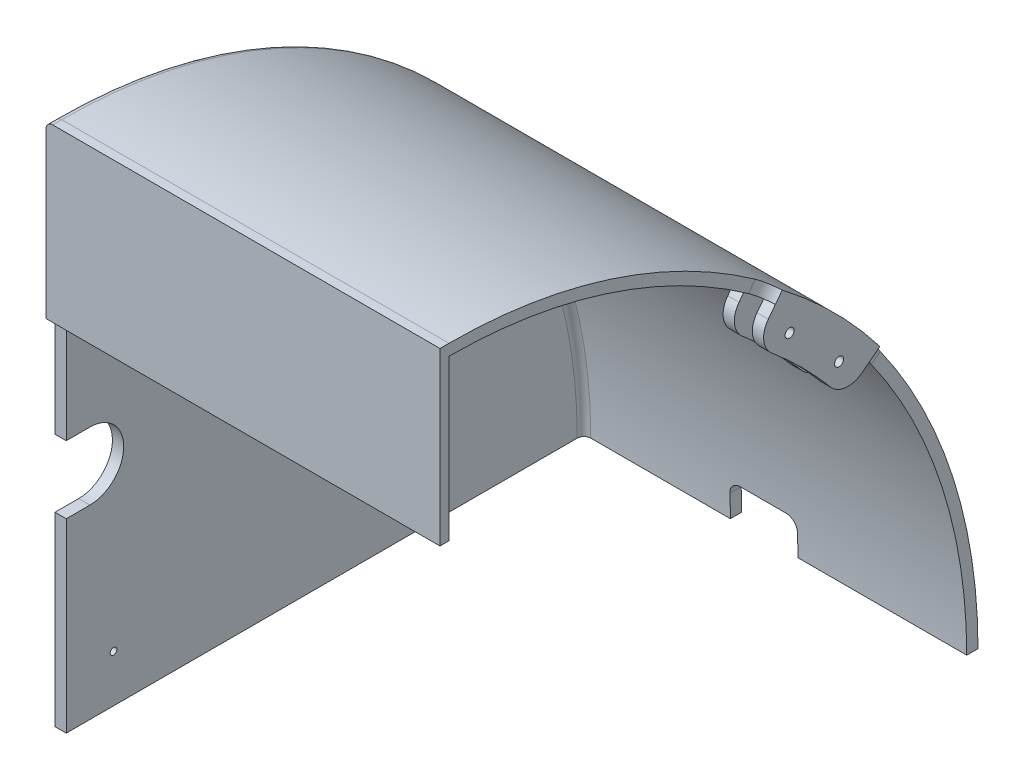
SolidWorks part; units mm, degrees
ref_plane "前视基准面" through (0, 0, 0) normal (0, 0, 1) x (1, 0, 0)
ref_plane "上视基准面" through (0, 0, 0) normal (0, 1, 0) x (1, 0, 0)
ref_plane "右视基准面" through (0, 0, 0) normal (1, 0, 0) x (0, 0, -1)
sketch "草图1" plane through (0, 0, 0) normal (1, 0, 0) x (0, 0, -1)
  circle A0 centre (0, 0) radius 235
  dimension "D1" = 470
extrude "凸台-拉伸1" add sketch "草图1" along normal blind 5
sketch "草图2" plane through (5, 0, 0) normal (1, 0, 0) x (0, 0, -1)
  circle A0 centre (0, 0) radius 230
  circle A1 centre (0, 0) radius 235
  circle A2 centre (0, 0) radius 235
  dimension "D1" = 0
  dimension "D2" = 5
extrude "凸台-拉伸2" add sketch "草图2" along normal blind 170
sketch "草图3" plane through (0, 0, 0) normal (-1, 0, 0) x (0, 0, 1)
  line L0 (0, 0) -> (0, 250)
  line L1 (0, 250) -> (330.8874, 250)
  line L2 (330.8874, 250) -> (330.8874, -253.4327)
  line L3 (330.8874, -253.4327) -> (-250, -253.4327)
  line L4 (-250, -253.4327) -> (-250, 0)
  line L5 (-250, 0) -> (0, 0)
  dimension "D1" = 250
  dimension "D2" = 250
extrude "切除-拉伸1" cut sketch "草图3" against normal through all
ref_plane "基准面1" through (167, 0, 0) normal (1, 0, 0) x (0, 0, -1)
sketch "草图4" plane through (167, 0, 0) normal (1, 0, 0) x (0, 0, -1)
  line L0 (0, 0) -> (35355.3391, 35355.3391) construction
  line L1 (230, 0) -> (0, 0) construction
  line L2 (170.571, 130.8837) -> (182.4713, 140.0151)
  line L3 (130.8837, 170.571) -> (140.0151, 182.4713)
  arc A0 (230, 0) -> (0, 230) centre (0, 0) ccw construction
  arc A1 (182.4713, 140.0151) -> (140.0151, 182.4713) centre (0, 0) ccw
  arc A2 (170.571, 130.8837) -> (130.8837, 170.571) centre (0, 0) ccw
  arc A4 (230, 0) -> (0, 230) centre (0, 0) ccw construction
  arc A5 (215, 0) -> (0, 215) centre (0, 0) ccw construction
  dimension "D2" = 45
  dimension "D3" = 7.5
  dimension "D1" = 15
extrude "凸台-拉伸3" add sketch "草图4" against normal blind 5
ref_plane "基准面2" through (59, 0, 0) normal (1, 0, 0) x (0, 0, -1)
sketch "草图5" plane through (59, 0, 0) normal (1, 0, 0) x (0, 0, -1)
  line L2 (170.571, 130.8837) -> (182.4713, 140.0151)
  line L3 (140.0151, 182.4713) -> (130.8837, 170.571)
  line L4 (170.571, 130.8837) -> (182.4713, 140.0151)
  line L5 (140.0151, 182.4713) -> (130.8837, 170.571)
  arc A2 (170.571, 130.8837) -> (130.8837, 170.571) centre (0, 0) ccw
  arc A3 (182.4713, 140.0151) -> (140.0151, 182.4713) centre (0, 0) ccw
  arc A4 (170.571, 130.8837) -> (130.8837, 170.571) centre (0, 0) ccw
  arc A5 (182.4713, 140.0151) -> (140.0151, 182.4713) centre (0, 0) ccw
  dimension "D1" = 0
extrude "凸台-拉伸4" add sketch "草图5" against normal blind 5
sketch "草图6" plane through (167, 0, 0) normal (1, 0, 0) x (0, 0, -1)
  line L2 (0, 0) -> (35355.3391, 35355.3391) construction
  line L3 (230, 0) -> (0, 0) construction
  line L4 (146.3012, 168.3002) -> (0, 0) construction
  line L5 (0, 0) -> (168.3002, 146.3012) construction
  circle A0 centre (146.3012, 168.3002) radius 2
  circle A1 centre (168.3002, 146.3012) radius 2
  dimension "D1" = 4
  dimension "D2" = 223
  dimension "D3" = 223
  dimension "D4" = 45
  dimension "D5" = 4
  dimension "D6" = 4
extrude "切除-拉伸2" cut sketch "草图6" against normal blind 5
fillet "圆角1" radius 3 2 edges at (0, 166.1701, -166.1701) (5, 162.6346, -162.6346)
sketch "草图7" plane through (175, 0, 0) normal (1, 0, 0) x (0, 0, -1)
  line L2 (170.571, 130.8837) -> (182.4713, 140.0151)
  line L3 (140.0151, 182.4713) -> (130.8837, 170.571)
  line L4 (170.571, 130.8837) -> (186.438, 143.0589)
  line L5 (143.0589, 186.438) -> (130.8837, 170.571)
  arc A0 (235, 0) -> (0, 235) centre (0, 0) ccw construction
  arc A1 (186.438, 143.0589) -> (143.0589, 186.438) centre (0, 0) ccw
  arc A2 (170.571, 130.8837) -> (130.8837, 170.571) centre (0, 0) ccw
  arc A3 (182.4713, 140.0151) -> (140.0151, 182.4713) centre (0, 0) ccw
  arc A4 (170.571, 130.8837) -> (130.8837, 170.571) centre (0, 0) ccw
  dimension "D1" = 0
extrude "凸台-拉伸5" add sketch "草图7" along normal blind 5
fillet "圆角2" radius 10 2 edges at (175, 184.4547, -141.537) (175, 141.537, -184.4547)
fillet "圆角3" radius 10 4 edges at (177.5, 130.8837, -170.571) (164.5, 130.8837, -170.571) (177.5, 170.571, -130.8837) (164.5, 170.571, -130.8837)
sketch "草图8" plane through (180, 0, 0) normal (1, 0, 0) x (0, 0, -1)
  circle A0 centre (168.3002, 146.3012) radius 2 construction
  circle A1 centre (146.3012, 168.3002) radius 2 construction
  circle A2 centre (168.3002, 146.3012) radius 2
  circle A3 centre (146.3012, 168.3002) radius 2
extrude "切除-拉伸3" cut sketch "草图8" against normal blind 5
fillet "圆角4" radius 10 2 edges at (56.5, 170.571, -130.8837) (56.5, 130.8837, -170.571)
sketch "草图11" plane through (0, 0, 0) normal (0, 0, 1) x (1, 0, 0)
  line L0 (3, 235) -> (175, 235) construction
  line L1 (3, 235) -> (175, 235)
  line L2 (0, 232) -> (0, 80) construction
  line L3 (0, 232) -> (0, 159)
  line L4 (175, 235) -> (175, 230) construction
  line L7 (0, 159) -> (175, 159)
  line L8 (175, 235) -> (175, 159)
  arc A0 (3, 235) -> (0, 232) centre (3, 232) ccw construction
  arc A1 (3, 235) -> (0, 232) centre (3, 232) ccw
  dimension "D1" = 76
extrude "凸台-拉伸7" add sketch "草图11" along normal blind 4
sketch "草图12" plane through (0, 0, 0) normal (-1, 0, 0) x (0, 0, 1)
  line L0 (0, 0) -> (-232, 0) construction
  line L2 (-101, 0) -> (-98, 0)
  line L3 (-224, 0) -> (-221, 0)
  line L6 (-161, 0) -> (-161, 50000) construction
  line L9 (-224, 0) -> (-221, 0)
  line L10 (-101, 0) -> (-98, 0)
  line L11 (-194.7226, 53.2145) -> (-193, 50.7543)
  line L12 (-203.8509, 46.1823) -> (-201.728, 44.0594)
  line L13 (-127.2774, 53.2145) -> (-129, 50.7543)
  line L14 (-118.1491, 46.1823) -> (-120.272, 44.0594)
  arc A0 (-101, 0) -> (-120.272, 44.0594) centre (-161, 0) ccw
  arc A1 (-98, 0) -> (-118.1491, 46.1823) centre (-161, 0) ccw
  circle A2 centre (-161, 0) radius 60 construction
  circle A3 centre (-161, 0) radius 63 construction
  arc A4 (-127.2774, 53.2145) -> (-194.7226, 53.2145) centre (-161, 0) ccw
  arc A5 (-129, 50.7543) -> (-193, 50.7543) centre (-161, 0) ccw
  arc A6 (-203.8509, 46.1823) -> (-224, 0) centre (-161, 0) ccw
  arc A7 (-201.728, 44.0594) -> (-221, 0) centre (-161, 0) ccw
  line M14 (-232, 0) -> (0, 0)
  dimension "D1" = 120
  dimension "D2" = 161
  dimension "D4" = 10
  dimension "D5" = 32
  dimension "D6" = 11
  dimension "D7" = 32
  dimension "D8" = 35
  dimension "D9" = 10
  dimension "D3" = 3
extrude "凸台-拉伸8" add sketch "草图12" along normal blind 20 contours A5 L13 A4 L11 | A1 L14 A0 M14 | A7 L12 A6 M14 region at (0, 24.2504, -105.559) region at (0, 0.5127, -222.5) region at (0, 62.3145, -161)
sketch "草图13" plane through (0, 0, 4) normal (0, 0, 1) x (1, 0, 0)
  line L1 (-36.5293, 28) -> (-2, 28)
  line L2 (-36.5293, 28) -> (-36.5293, -16.1335)
  line L3 (-36.5293, -16.1335) -> (-2, -16.1335)
  line L4 (-2, 28) -> (-2, -16.1335)
  line L5 (175, 0) -> (8, 0) construction
  dimension "D1" = 2
  dimension "D2" = 28
extrude "切除-拉伸5" cut sketch "草图13" against normal blind 120 from offset 120 offset against normal yes
sketch "草图14" plane through (0, 0, 0) normal (0, 0, 1) x (1, 0, 0)
  line L0 (175, 0) -> (8, 0) construction
  line L1 (70, 15) -> (100, 15)
  line L2 (70, 15) -> (70, -15)
  line L3 (70, -15) -> (100, -15)
  line L4 (100, 15) -> (100, -15)
  line L6 (5, 0) -> (5, 227) construction
  dimension "D1" = 30
  dimension "D2" = 15
  dimension "D3" = 30
  dimension "D4" = 65
extrude "切除-拉伸8" cut sketch "草图14" against normal through all
fillet "圆角5" radius 5 2 edges at (70, 15, -232.0156) (100, 15, -232.0156)
sketch "草图15" plane through (0, 0, 0) normal (-1, 0, 0) x (0, 0, 1)
  line L0 (4, 232) -> (4, 159) construction
  line L1 (0, 0) -> (-98, 0) construction
  line L2 (-10.5, 82.5) -> (0, 82.5)
  line L3 (0, 159) -> (0, 0) construction
  line L4 (0, 82.5) -> (0, 112.5)
  line L5 (0, 112.5) -> (-10.5, 112.5)
  arc A0 (-10.5, 112.5) -> (-10.5, 82.5) centre (-10.5, 97.5) ccw
  dimension "D1" = 30
  dimension "D2" = 14.5
  dimension "D3" = 97.5
extrude "切除-拉伸9" cut sketch "草图15" against normal blind 10
sketch "草图16" plane through (0, 0, 0) normal (-1, 0, 0) x (0, 0, 1)
  line L0 (0, 0) -> (-98, 0) construction
  line L1 (-21, 21) -> (26.8267, 21) construction
  line L2 (-21, 21) -> (-21, -23.6076) construction
  line L3 (-21, -23.6076) -> (26.8267, -23.6076) construction
  line L4 (26.8267, 21) -> (26.8267, -23.6076) construction
  line L5 (0, 82.5) -> (0, 0) construction
  circle A0 centre (-21, 21) radius 1.5
  dimension "D3" = 3
  dimension "D1" = 21
  dimension "D2" = 21
extrude "切除-拉伸10" cut sketch "草图16" against normal blind 10
chamfer "倒角1" distance 0.5 angle 45 1 edges at (0, 21, -19.5)
